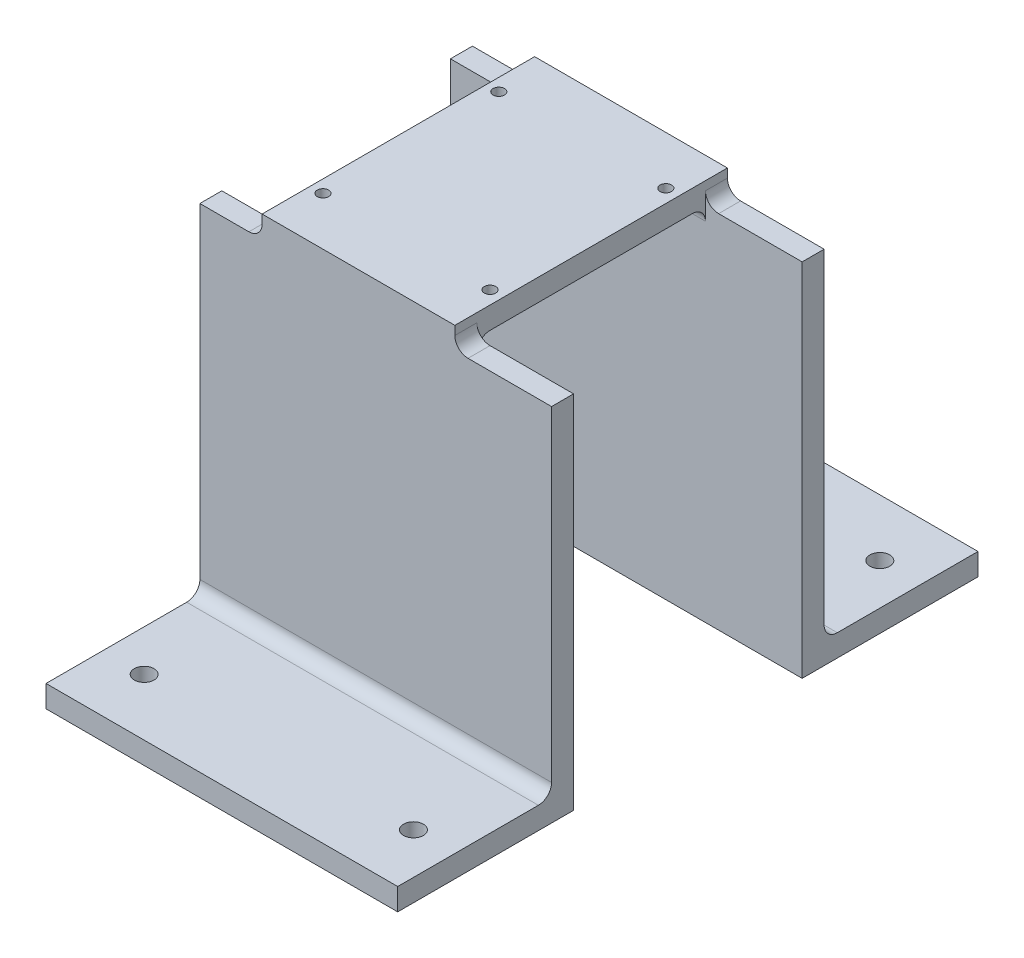
SolidWorks part; units mm, degrees
ref_plane "Front Plane" through (0, 0, 0) normal (0, 0, 1) x (1, 0, 0)
ref_plane "Top Plane" through (0, 0, 0) normal (0, 1, 0) x (1, 0, 0)
ref_plane "Right Plane" through (0, 0, 0) normal (1, 0, 0) x (0, 0, -1)
sketch "Sketch1" plane through (0, 0, 0) normal (0, 1, 0) x (1, 0, 0)
  line L0 (0, 0) -> (0, 66) construction
  line L1 (-40, 66) -> (40, 66)
  line L2 (-40, 66) -> (-40, 26)
  line L3 (-40, 26) -> (40, 26)
  line L4 (40, 66) -> (40, 26)
  line L5 (0, 0) -> (-30.625, 53.0441) construction
  line L6 (-55, 0) -> (55, 0) construction
  line L7 (40, -66) -> (40, -26)
  line L8 (-40, -26) -> (40, -26)
  line L9 (-40, -66) -> (-40, -26)
  line L10 (-40, -66) -> (40, -66)
  circle A0 centre (-30.625, 53.0441) radius 2.25
  circle A1 centre (30.625, 53.0441) radius 2.25
  circle A2 centre (30.625, -53.0441) radius 2.25
  circle A3 centre (-30.625, -53.0441) radius 2.25
  point P9 (0, 0)
  dimension "D7" = 4.5
  dimension "D1" = 26
  dimension "D2" = 40
  dimension "D3" = 80
  dimension "D4" = 40
  dimension "D5" = 61.25
  dimension "D6" = 30
extrude "Boss-Extrude1" add sketch "Sketch1" along normal blind 5
sketch "Sketch2" plane through (0, 5, 0) normal (0, 1, 0) x (1, 0, 0)
  line L0 (40, 26) -> (40, 66) construction
  line L1 (-40, 26) -> (40, 26)
  line L2 (-40, 26) -> (-40, 31)
  line L3 (-40, 31) -> (40, 31)
  line L4 (40, 26) -> (40, 31)
  line L5 (-55, 0) -> (55, 0) construction
  line L6 (40, -26) -> (40, -31)
  line L7 (-40, -31) -> (40, -31)
  line L8 (-40, -26) -> (-40, -31)
  line L9 (-40, -26) -> (40, -26)
  dimension "D1" = 5
extrude "Boss-Extrude2" add sketch "Sketch2" along normal blind 77.05
sketch "Sketch3" plane through (0, 82.05, 0) normal (0, 1, 0) x (1, 0, 0)
  line L1 (-25.85, 31) -> (18, 31)
  line L2 (-25.85, 31) -> (-25.85, -31)
  line L3 (-25.85, -31) -> (18, -31)
  line L4 (18, 31) -> (18, -31)
  line L5 (40, -66) -> (40, -31) construction
  line L7 (-40, -31) -> (40, -31) construction
  point P5 (3.85, -28)
  point P8 (-112.3481, 31.7358)
  dimension "D1" = 62
  dimension "D2" = 43.85
  dimension "D3" = 22
  dimension "D4" = 0
extrude "Boss-Extrude3" add sketch "Sketch3" along normal blind 5 contours L2 L3 L4 L1
sketch "Sketch4" plane through (0, 87.05, 0) normal (0, 1, 0) x (1, 0, 0)
  line L1 (-23, 20) -> (15, 20) construction
  line L2 (-23, 20) -> (-23, -20) construction
  line L3 (-23, -20) -> (15, -20) construction
  line L4 (15, 20) -> (15, -20) construction
  circle A0 centre (-23, 20) radius 1.3
  circle A1 centre (15, 20) radius 1.3
  circle A2 centre (15, -20) radius 1.3
  circle A3 centre (-23, -20) radius 1.3
  dimension "D5" = 2.6
  dimension "D1" = 23
  dimension "D2" = 40
  dimension "D3" = 38
  dimension "D4" = 20
extrude "Cut-Extrude1" cut sketch "Sketch4" against normal up to next
fillet "Fillet1" radius 3 4 edges at (-3.925, 82.05, -26) (-3.925, 82.05, 26) (0, 5, -31) (0, 5, 31)
fillet "Fillet2" radius 3 4 edges at (18, 82.05, -28.5) (-25.85, 82.05, -28.5) (-25.85, 82.05, 28.5) (18, 82.05, 28.5)
